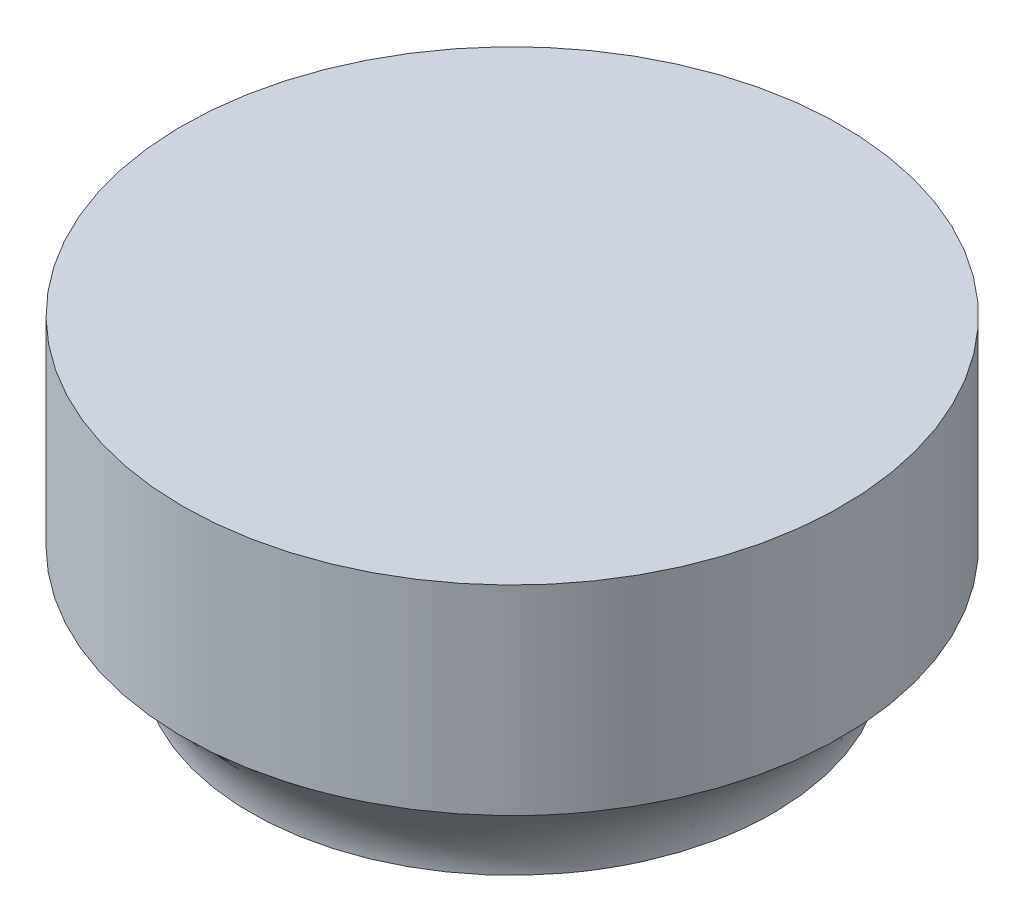
SolidWorks part; units mm, degrees
ref_plane "Front Plane" through (0, 0, 0) normal (0, 0, 1) x (1, 0, 0)
ref_plane "Top Plane" through (0, 0, 0) normal (0, 1, 0) x (1, 0, 0)
ref_plane "Right Plane" through (0, 0, 0) normal (1, 0, 0) x (0, 0, -1)
sketch "Sketch1" plane through (0, 0, 0) normal (0, 1, 0) x (1, 0, 0)
  circle A0 centre (0, 0) radius 32.75
  dimension "D1" = 65.5
ref_plane "Plane1" through (0, 12.5, 0) normal (0, 1, 0) x (1, 0, 0)
sketch "Sketch2" plane through (0, 12.5, 0) normal (0, 1, 0) x (1, 0, 0)
  circle A0 centre (0, 0) radius 41.275
  dimension "D1" = 82.55
loft "Loft1" add profiles "Sketch1", "Sketch2" connector at (-31.1344, 0, -10.1594) connector at (-23.8393, 12.5, -33.6944)
sketch "Sketch3" plane through (0, 12.5, 0) normal (0, 1, 0) x (1, 0, 0)
  circle A0 centre (0, 0) radius 41.275
extrude "Boss-Extrude1" add sketch "Sketch3" along normal blind 25
